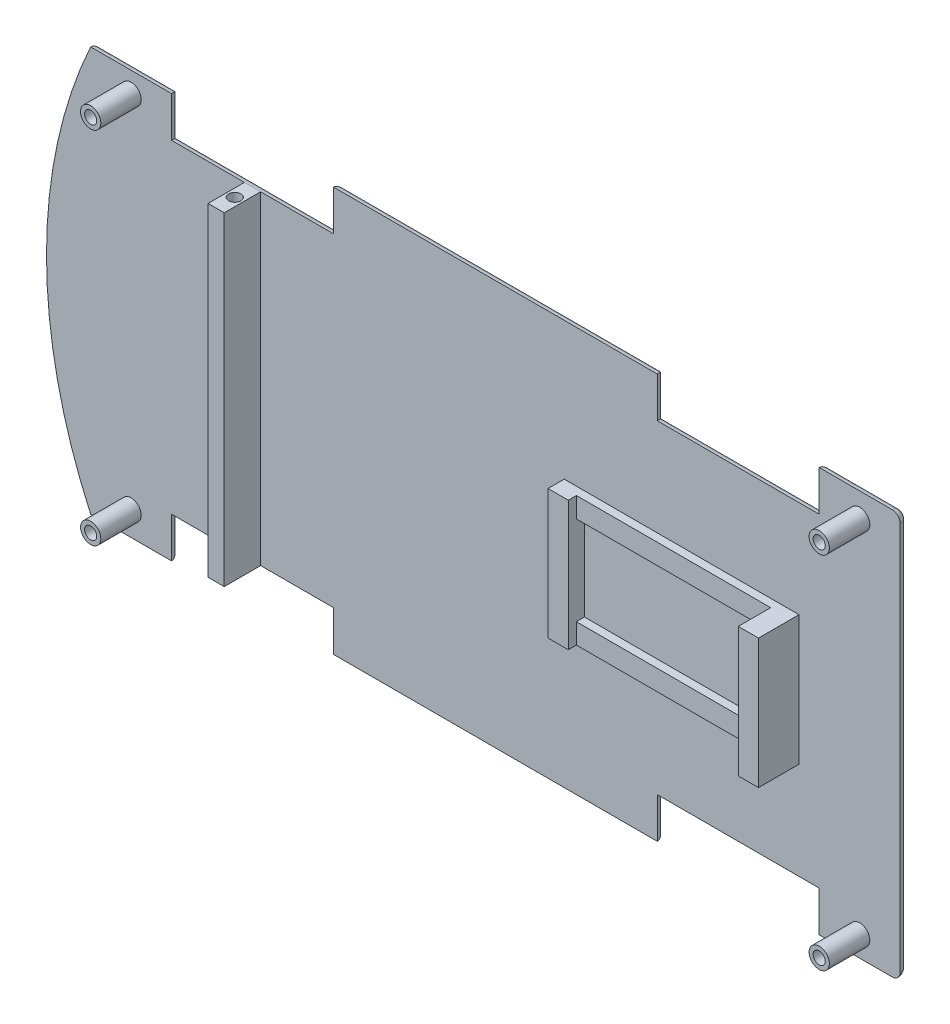
SolidWorks part; units mm, degrees
ref_plane "Front Plane" through (0, 0, 0) normal (0, 0, 1) x (1, 0, 0)
ref_plane "Top Plane" through (0, 0, 0) normal (0, 1, 0) x (1, 0, 0)
ref_plane "Right Plane" through (0, 0, 0) normal (1, 0, 0) x (0, 0, -1)
sketch "Sketch2" plane through (0, 0, 0) normal (0, 0, 1) x (1, 0, 0)
  line L1 (-50, -25) -> (-40, -25)
  line L3 (-50, 25) -> (-40, 25)
  line L4 (50, -25) -> (50, 25)
  line L5 (-50, -25) -> (50, 25) construction
  line L6 (-50, 25) -> (50, -25) construction
  line L8 (-40, -25) -> (-40, -20)
  line L9 (-40, -20) -> (-20, -20)
  line L10 (-20, -25) -> (-20, -20)
  line L11 (20, -25) -> (20, -20)
  line L12 (20, -20) -> (40, -20)
  line L13 (40, -25) -> (40, -20)
  line L14 (20, 20) -> (40, 20)
  line L15 (20, 20) -> (20, 25)
  line L17 (40, 20) -> (40, 25)
  line L18 (-40, 20) -> (-20, 20)
  line L19 (-40, 20) -> (-40, 25)
  line L21 (-20, 20) -> (-20, 25)
  line L22 (-20, 25) -> (20, 25)
  line L23 (-40, 25) -> (-20, 25) [skipped]
  line L24 (20, 25) -> (40, 25) [skipped]
  line L25 (40, 25) -> (50, 25)
  line L26 (-20, -25) -> (20, -25)
  line L27 (40, -25) -> (50, -25)
  arc A0 (-50, 25) -> (-50, -25) centre (4.5436, 0) ccw
  point P0 (0, 0)
  dimension "D3" = 60
  dimension "D1" = 50
  dimension "D2" = 100
  dimension "D4" = 20
  dimension "D5" = 5
  dimension "D6" = 10
  dimension "D9" = 10
  dimension "D7" = 2
  dimension "D8" = 2
extrude "Boss-Extrude1" add sketch "Sketch2" along normal blind 1
sketch "Sketch3" plane through (0, 0, 1) normal (0, 0, 1) x (1, 0, 0)
  line L0 (-60.1295, 0) -> (81.5202, 0) construction
  line L1 (30, 20) -> (30, -20) construction
  line L2 (40, 20) -> (20, 20) construction
  line L3 (20, -20) -> (40, -20) construction
  line L4 (8.5, 8) -> (37.5, 8)
  line L5 (11, -5.5) -> (35, -5.5)
  line L6 (11, -5.5) -> (11, 5.5)
  line L7 (11, 5.5) -> (35, 5.5)
  line L8 (35, -5.5) -> (35, 5.5)
  line L9 (11, -5.5) -> (35, 5.5) construction
  line L10 (11, 5.5) -> (35, -5.5) construction
  line L11 (37.5, -8) -> (37.5, 8)
  line L12 (8.5, -8) -> (37.5, -8)
  line L13 (8.5, -8) -> (8.5, 8)
  point P9 (23, 0)
  dimension "D1" = 5
  dimension "D2" = 24
  dimension "D3" = 11
  dimension "D4" = 2.5
extrude "Boss-Extrude2" add sketch "Sketch3" along normal blind 1
sketch "Sketch4" plane through (0, 0, 2) normal (0, 0, 1) x (1, 0, 0)
  line L0 (37.5, -8) -> (37.5, 8) construction
  line L1 (37.5, 8) -> (35, 8)
  line L2 (37.5, 8) -> (37.5, -8)
  line L3 (37.5, -8) -> (35, -8)
  line L4 (35, 8) -> (35, -8)
  line L5 (37.5, 8) -> (8.5, 8) construction
  line L6 (8.5, -8) -> (37.5, -8) construction
  line L7 (35, -5.5) -> (35, 5.5) construction
extrude "Boss-Extrude3" add sketch "Sketch4" along normal blind 4
sketch "Sketch5" plane through (0, 0, 2) normal (0, 0, 1) x (1, 0, 0)
  line L0 (37.5, 8) -> (8.5, 8) construction
  line L1 (11, 8) -> (8.5, 8)
  line L2 (11, 8) -> (11, -8)
  line L3 (11, -8) -> (8.5, -8)
  line L4 (8.5, 8) -> (8.5, -8)
extrude "Boss-Extrude4" add sketch "Sketch5" along normal blind 1
sketch "Sketch6" plane through (0, 0, 1) normal (0, 0, 1) x (1, 0, 0)
  line L0 (-40, -25) -> (-40, -20) construction
  line L2 (-50, -25) -> (-40, -25) construction
  line L3 (50, -25) -> (50, 25) construction
  line L4 (50, 25) -> (40, 25) construction
  circle A0 centre (-45, -22) radius 0.75
  circle A1 centre (-45, -22) radius 1.25
  circle A2 centre (44.9988, -22.4624) radius 0.75
  circle A3 centre (44.9988, -22.4624) radius 1.25
  circle A4 centre (45, 22) radius 0.75
  circle A5 centre (45, 22) radius 1.25
  circle A6 centre (-44.9988, 22.4624) radius 0.75
  circle A7 centre (-44.9988, 22.4624) radius 1.25
  dimension "D1" = 1.5
  dimension "D3" = 5
  dimension "D7" = 5.0012
  dimension "D4" = 3
  dimension "D8" = 3
  dimension "D9" = 5
  dimension "D2" = 0.5
  dimension "D5" = 2
  dimension "D6" = 2
extrude "Boss-Extrude5" add sketch "Sketch6" along normal blind 5
sketch "Sketch7" plane through (0, 0, 1) normal (0, 0, 1) x (1, 0, 0)
  line L0 (-30, -20) -> (-30, 20) construction
  line L1 (-40, -20) -> (-20, -20) construction
  line L2 (-20, 20) -> (-40, 20) construction
  line L4 (-29, -20) -> (-31, -20)
  line L5 (-29, -20) -> (-29, 20)
  line L6 (-29, 20) -> (-31, 20)
  line L7 (-31, -20) -> (-31, 20)
  line L8 (-29, -20) -> (-31, 20) construction
  line L9 (-29, 20) -> (-31, -20) construction
  point P6 (-30, 0)
  dimension "D1" = 2
extrude "Boss-Extrude6" add sketch "Sketch7" along normal blind 4.5
sketch "Sketch8" plane through (0, -20, 0) normal (0, -1, 0) x (1, 0, 0)
  line L0 (-29, 1) -> (-20, 1) construction
  line L1 (-30, 5.5) -> (-30, -0.9294) construction
  line L2 (-31, 5.5) -> (-29, 5.5) construction
  circle A0 centre (-30, 3.2) radius 0.75
  dimension "D2" = 1.5
  dimension "D1" = 2.2
extrude "Cut-Extrude1" cut sketch "Sketch8" against normal through all
fillet "Fillet1" radius 1 22 edges at (40, 22.5, 0) (30, 20, 0) (20, 22.5, 0) (0, 25, 0) (-20, 22.5, 0) (-30, 20, 0) (-40, 22.5, 0) (-45, 25, 0) (-55.4564, 0, 0) (-45, -25, 0) (-40, -22.5, 0) (-30, -20, 0) (-20, -22.5, 0) (0, -25, 0) (20, -22.5, 0) (30, -20, 0) (40, -22.5, 0) (45, -25, 0) (50, 0, 0) (45, 25, 0) (50, 25, 0.5) (50, -25, 0.5)
